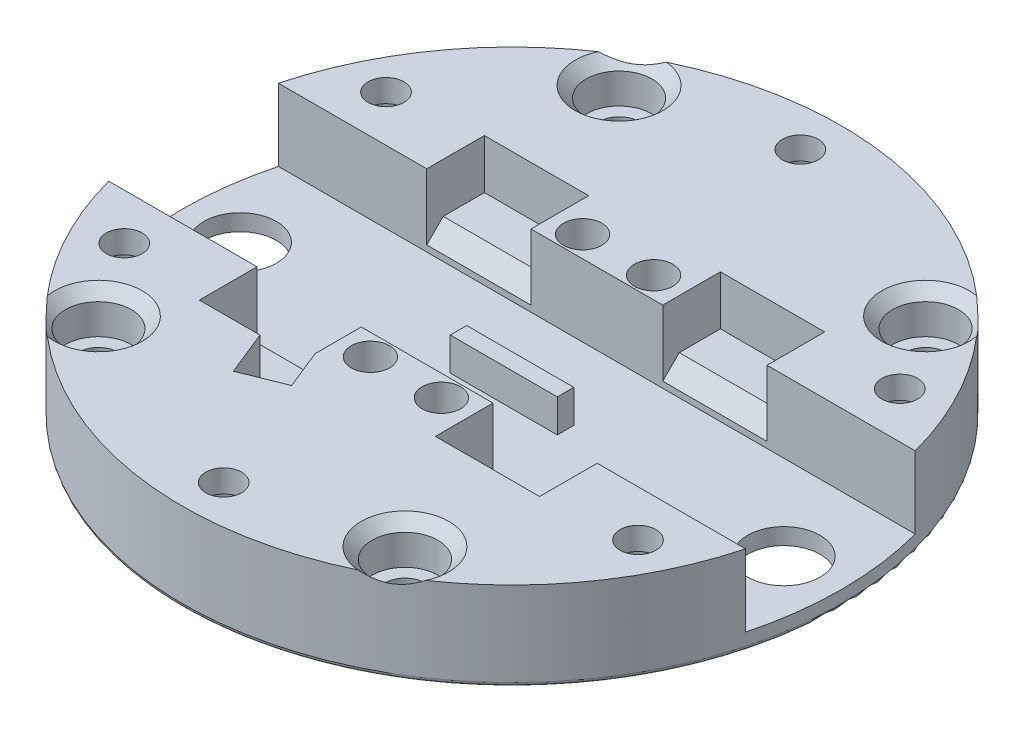
SolidWorks part; units mm, degrees
material "ABS"
ref_plane "Front Plane" through (0, 0, 0) normal (0, 0, 1) x (1, 0, 0)
ref_plane "Top Plane" through (0, 0, 0) normal (0, 1, 0) x (1, 0, 0)
ref_plane "Right Plane" through (0, 0, 0) normal (1, 0, 0) x (0, 0, -1)
ref_plane "Plane1" through (0, 10.75, 0) normal (0, 1, 0) x (1, 0, 0)
sketch "Sketch1" plane through (0, 10.75, 0) normal (0, 1, 0) x (1, 0, 0)
  line L0 (-13.2959, -23.5983) -> (-13.2959, -17.3)
  line L1 (-13.2959, -17.3) -> (-12.5898, -15.9012)
  line L2 (-12.5898, -15.9012) -> (5.7627, -15.9012)
  line L3 (5.7627, -15.9012) -> (-13.2959, -23.5983)
  circle A0 centre (0, 0) radius 40
extrude "Boss-Extrude1" add sketch "Sketch1" against normal blind 10.75
sketch "Sketch2" plane through (0, 10.75, 0) normal (0, 1, 0) x (-1, 0, 0)
  line L0 (12.5898, 15.9012) -> (13.2959, 15.9012)
  line L1 (13.2959, 15.9012) -> (13.2959, 17.3)
  line L2 (13.2959, 17.3) -> (12.5898, 15.9012)
extrude "Cut-Extrude1" cut sketch "Sketch2" against normal blind 6
sketch "Sketch3" plane through (0, 10.75, 0) normal (0, 1, 0) x (-1, 0, 0)
  line L0 (38.6511, 10.3) -> (-38.6511, 10.3)
  arc A0 (-38.6511, 10.3) -> (38.6511, 10.3) centre (0, 0) ccw
extrude "Cut-Extrude2" cut sketch "Sketch3" against normal blind 6
ref_plane "Plane2" through (-13.2959, 0, 0) normal (-1, 0, 0) x (0, -1, 0)
sketch "Sketch4" plane through (-13.2959, 0, 0) normal (-1, 0, 0) x (0, -1, 0)
  line L0 (-4.75, 10.3) -> (-4.75, 15.9012)
  line L1 (-4.75, 15.9012) -> (-10.75, 15.9012)
  line L2 (-10.75, 15.9012) -> (-10.75, 10.3)
  line L3 (-10.75, 10.3) -> (-4.75, 10.3)
extrude "Cut-Extrude3" cut sketch "Sketch4" against normal blind 0.7061
sketch "Sketch5" plane through (-12.5898, 0, 0) normal (-1, 0, 0) x (0, 0, 1)
  line L0 (10.3, 4.75) -> (15.9012, 4.75)
  line L1 (15.9012, 4.75) -> (15.9012, 10.75)
  line L2 (15.9012, 10.75) -> (10.3, 10.75)
  line L3 (10.3, 10.75) -> (10.3, 4.75)
extrude "Cut-Extrude4" cut sketch "Sketch5" against normal blind 4.5898
sketch "Sketch6" plane through (-13.2959, 0, 0) normal (1, 0, 0) x (0, 0, -1)
  line L0 (-10.3, 10.75) -> (-17.3, 10.75)
  line L1 (-17.3, 10.75) -> (-17.3, 4.75)
  line L2 (-17.3, 4.75) -> (-10.3, 4.75)
  line L3 (-10.3, 4.75) -> (-10.3, 10.75)
extrude "Cut-Extrude5" cut sketch "Sketch6" against normal blind 7.3553
ref_plane "Plane3" through (0, 2, 0) normal (0, -1, 0) x (1, 0, 0)
sketch "Sketch7" plane through (0, 2, 0) normal (0, -1, 0) x (1, 0, 0)
  line L0 (38.6511, 10.3) -> (-38.6511, 10.3)
  arc A0 (-38.6511, 10.3) -> (38.6511, 10.3) centre (0, 0) ccw
extrude "Cut-Extrude6" cut sketch "Sketch7" against normal up to next
sketch "Sketch8" plane through (0, 10.75, 0) normal (0, 1, 0) x (-1, 0, 0)
  line L0 (-8, 10.3) -> (-8, 17.3)
  line L1 (-8, 17.3) -> (-20.6511, 17.3)
  line L2 (-20.6511, 17.3) -> (-20.6511, 10.3)
  line L3 (-20.6511, 10.3) -> (-8, 10.3)
extrude "Cut-Extrude7" cut sketch "Sketch8" against normal blind 6
sketch "Sketch9" plane through (0, 2, 0) normal (0, 1, 0) x (-1, 0, 0)
  line L0 (-38.6511, -10.3) -> (38.6511, -10.3)
  arc A0 (38.6511, -10.3) -> (-38.6511, -10.3) centre (0, 0) cw
extrude "Boss-Extrude2" add sketch "Sketch9" along normal blind 8.75
sketch "Sketch10" plane through (0, 10.75, 0) normal (0, 1, 0) x (-1, 0, 0)
  line L0 (-20.6511, -10.3) -> (-20.6511, -17.3)
  line L1 (-20.6511, -17.3) -> (-8, -17.3)
  line L2 (-8, -17.3) -> (-8, -10.3)
  line L3 (-8, -10.3) -> (-20.6511, -10.3)
extrude "Cut-Extrude8" cut sketch "Sketch10" against normal blind 6
sketch "Sketch11" plane through (0, 10.75, 0) normal (0, 1, 0) x (-1, 0, 0)
  line L0 (8, -10.3) -> (8, -17.3)
  line L1 (8, -17.3) -> (20.6511, -17.3)
  line L2 (20.6511, -17.3) -> (20.6511, -10.3)
  line L3 (20.6511, -10.3) -> (8, -10.3)
extrude "Cut-Extrude9" cut sketch "Sketch11" against normal blind 6
sketch "Sketch12" plane through (0, 2, 0) normal (0, 1, 0) x (-1, 0, 0)
  line L0 (6.5, -1) -> (-6.5, -1)
  line L1 (-6.5, -1) -> (-6.5, 1)
  line L2 (-6.5, 1) -> (6.5, 1)
  line L3 (6.5, 1) -> (6.5, -1)
extrude "Boss-Extrude3" add sketch "Sketch12" along normal blind 4
draft "Draft1" type of draft neutral plane draft angle 68.008 faces to draft 1 face at (-4.9424, 5.1667, 15.9012) neutral plane through (-8, 0, 0) neutral plane normal (-1, 0, 0) parameters "D1"=68.008
draft "Draft2" type of draft neutral plane draft angle 21.992 faces to draft 1 face at (-13.2959, 5.25, 19.8193) neutral plane through (-20.6511, 10.75, 17.3) neutral plane normal (0, 0, -1) parameters "D1"=21.992
hole_wizard "M4 Clearance Hole1" positions "Sketch14" profile "Sketch13" hole size "M4" standard "ANSI Metric"
sketch "Sketch14" plane through (0, 0, 0) normal (0, -1, 0) x (-1, 0, 0)
  point P0 (-4.3075, -12.8792)
  point P1 (4.3075, 12.8792)
  point P2 (-4.3075, 12.8792)
  point P3 (4.3075, -12.8792)
sketch "Sketch13" plane through (4.3075, 0, 12.8792) normal (1, 0, 0) x (0, 0, -1)
  line L0 (0, 0) -> (0, 10.75)
  line L1 (0, 10.75) -> (2.33, 10.75)
  line L2 (2.33, 10.75) -> (2.33, 0)
  line L5 (2.33, 0) -> (0, 0)
  line L11 (0, -6.35) -> (0, 107.95) construction
  dimension "Thru Hole Dia." = 4.66
  dimension "Thru Hole Depth" = 10.75
hole_wizard "CBORE for M4 Hex Head Machine Screw1" positions "Sketch16" profile "Sketch15" counterbore size "M4" standard "ANSI Metric"
sketch "Sketch16" plane through (0, 10.75, 0) normal (0, 1, 0) x (1, 0, 0)
  point P0 (25.1023, 25.1023)
  point P1 (-17.75, 30.7439)
  point P2 (-25.1023, -25.1023)
  point P3 (17.75, -30.7439)
sketch "Sketch15" plane through (25.1023, 10.75, -25.1023) normal (1, 0, 0) x (0, 0, 1)
  line L0 (0, 0) -> (0, 10.75)
  line L1 (0, 10.75) -> (2.4, 10.75)
  line L3 (2.4, 10.75) -> (2.4, 5)
  line L4 (4, 5) -> (2.4, 5)
  line L5 (4, 5) -> (4, 1.32)
  line L6 (4, 1.32) -> (5.32, 0)
  line L7 (5.32, 0) -> (0, 0)
  line L8 (-4, 1.32) -> (-5.32, 0) construction
  line L11 (0, -6.35) -> (0, 107.95) construction
  dimension "Thru Hole Dia." = 4.8
  dimension "Thru Hole Depth" = 10.75
  dimension "C'Bore Dia." = 8
  dimension "C'Bore Depth" = 5
  dimension "Near C'Sink Dia." = 10.64
  dimension "Near C'Sink Angle" = 90
hole_wizard "Ø8.8 (8.8) Diameter Hole1" positions "Sketch18" profile "Sketch17" hole size "Ø8.8" standard "ANSI Metric"
sketch "Sketch18" plane through (0, 0, 0) normal (0, -1, 0) x (-1, 0, 0)
  point P0 (33, 0)
  point P1 (-33, 0)
sketch "Sketch17" plane through (-33, 0, 0) normal (1, 0, 0) x (0, 0, -1)
  line L0 (0, 0) -> (0, 10.75)
  line L1 (0, 10.75) -> (4.4, 10.75)
  line L2 (4.4, 10.75) -> (4.4, 0)
  line L5 (4.4, 0) -> (0, 0)
  line L11 (0, -6.35) -> (0, 107.95) construction
  dimension "Thru Hole Dia." = 8.8
  dimension "Thru Hole Depth" = 10.75
hole_wizard "CBORE for M4 Hex Head Machine Screw2" positions "Sketch20" profile "Sketch19" counterbore size "M4" standard "ANSI Metric"
sketch "Sketch20" plane through (0, 0, 0) normal (0, -1, 0) x (-1, 0, 0)
  point P0 (31.1852, -15.8897)
  point P1 (0, -35)
  point P2 (-31.1852, -15.8897)
  point P3 (31.1852, 15.8897)
  point P4 (0, 35)
  point P5 (-31.1852, 15.8897)
sketch "Sketch19" plane through (-31.1852, 0, 15.8897) normal (1, 0, 0) x (0, 0, -1)
  line L0 (0, 0) -> (0, 10.75)
  line L1 (0, 10.75) -> (2.175, 10.75)
  line L3 (2.175, 10.75) -> (2.175, 8)
  line L4 (2.175, 8) -> (3.9, 8)
  line L5 (3.9, 8) -> (3.9, 0)
  line L7 (3.9, 0) -> (0, 0)
  line L11 (0, -6.35) -> (0, 107.95) construction
  dimension "Thru Hole Dia." = 4.35
  dimension "Thru Hole Depth" = 10.75
  dimension "C'Bore Dia." = 7.8
  dimension "C'Bore Depth" = 8
chamfer "Chamfer1" distance 2 angle 45 4 edges at (14.3256, 4.75, 10.3) (14.3256, 4.75, -10.3) (-14.3256, 4.75, -10.3) (-14.3256, 4.75, 10.3)
chamfer "Chamfer2" distance 1.5312 angle 63.216 1 edges at (-10.04, 1.65, 10.85) first distance on face at (-11.4887, 2.56, 13.72)
fillet "Fillet1" radius 0.5 1 edges at (0, 0, -40) tangent propagation no
